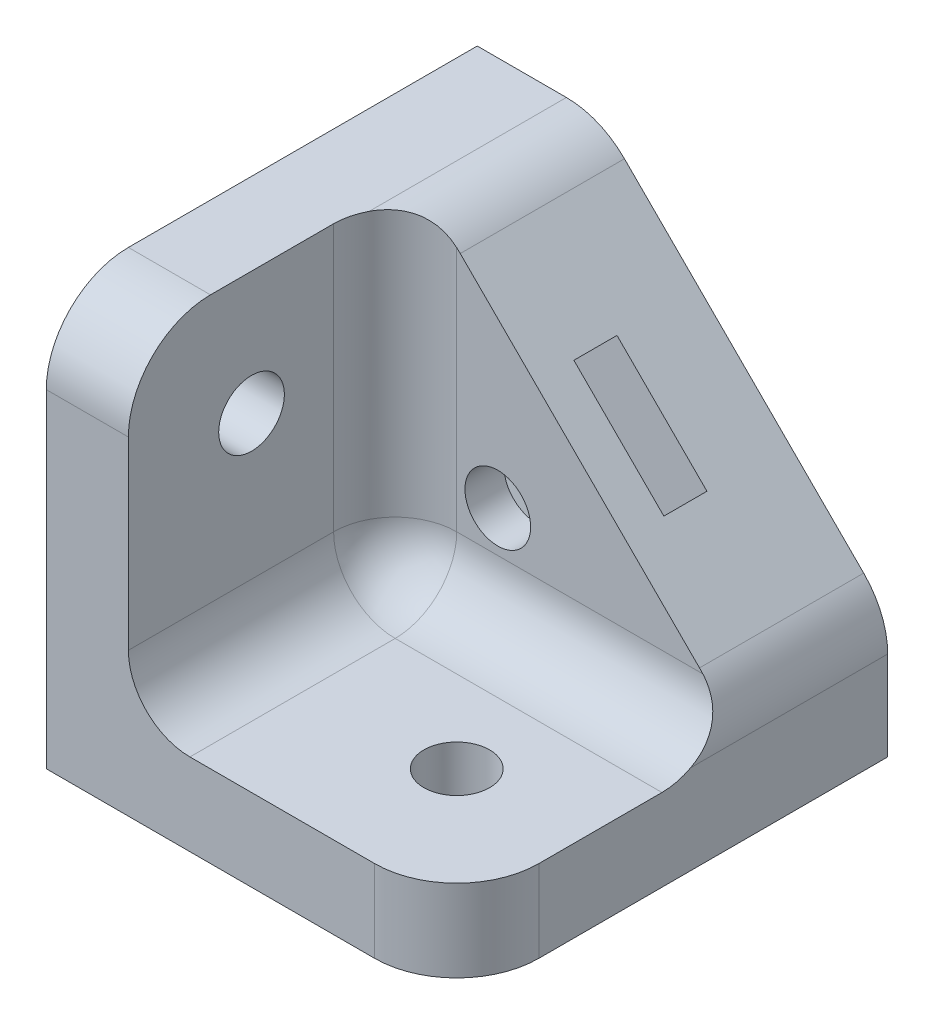
SolidWorks part; units mm, degrees
ref_plane "Front Plane" through (0, 0, 0) normal (0, 0, 1) x (1, 0, 0)
ref_plane "Top Plane" through (0, 0, 0) normal (0, 1, 0) x (1, 0, 0)
ref_plane "Right Plane" through (0, 0, 0) normal (1, 0, 0) x (0, 0, -1)
sketch "Sketch4" plane through (0, 0, 0) normal (0, 0, 1) x (1, 0, 0)
  line L2 (0, 0) -> (0, 20)
  line L3 (0, 20) -> (4, 20)
  line L4 (4, 4) -> (4, 20)
  line L5 (0, 0) -> (20, 0)
  line L7 (4, 4) -> (20, 4)
  line L8 (20, 0) -> (20, 4)
  line L9 (4, 20) -> (6, 20)
  line L10 (6, 20) -> (20, 6)
  line L11 (20, 6) -> (20, 4)
  dimension "D1" = 4
  dimension "D2" = 4
  dimension "D3" = 20
  dimension "D4" = 20
  dimension "D5" = 2
  dimension "D6" = 2
extrude "Boss-Extrude4" add sketch "Sketch4" along normal blind 8 separate body contours L5 L8 L7 L4 L3 L2 | L4 L7 region at (0.2828, 10, 0) region at (9.9325, 9.9325, 0)
extrude "Boss-Extrude5" add sketch "Sketch4<4>" along normal blind 21 contours L5 L8 L7 L4 L3 L2 region at (0.2828, 10, 0)
sketch "Sketch4<4>" plane through (0, 0, 0) normal (0, 0, 1) x (1, 0, 0) same geometry as "Sketch4"
sketch "Sketch5" plane through (13, 13, 0) normal (0.7071, 0.7071, 0) x (0, 0, -1)
  line L1 (-6.1, -3.1) -> (-4, -3.1)
  line L2 (-6.1, -3.1) -> (-6.1, 3.1)
  line L3 (-6.1, 3.1) -> (-4, 3.1)
  line L4 (-4, -3.1) -> (-4, 3.1)
  line L5 (-6.1, -3.1) -> (-4, 3.1) construction
  line L6 (-6.1, 3.1) -> (-4, -3.1) construction
  line L8 (0, 9.8995) -> (0, -9.8995) construction
  point P0 (-5.05, 0)
  dimension "D1" = 2.1
  dimension "D2" = 4
  dimension "D3" = 6.2
extrude "Cut-Extrude1" cut sketch "Sketch5" against normal blind 9
hole_wizard "Ø3.2 (3.2) Diameter Hole1" positions "3DSketch2" profile "Sketch6" hole size "Ø3.2" standard "ANSI Metric" end condition through all
sketch3d "3DSketch2"
  line L0 (0, 0, 21) -> (0, 0, 0) construction
  line L1 (0, 0, 0) -> (20, 0, 0) construction
  line L2 (0, 0, 0) -> (0, 20, 0) construction
  point P0 (14, 0, 15)
  point P2 (0, 14, 15)
  point P4 (9, 9, 0)
  dimension "D1" = 14
  dimension "D2" = 14
  dimension "D3" = 15
  dimension "D4" = 15
  dimension "D5" = 9
  dimension "D6" = 9
sketch "Sketch6" plane through (14, 0, 15) normal (1, 0, 0) x (0, 0, -1)
  line L0 (0, 0) -> (0, 20)
  line L1 (0, 20) -> (1.6, 20)
  line L2 (1.6, 20) -> (1.6, 0)
  line L5 (1.6, 0) -> (0, 0)
  line L11 (0, -6.35) -> (0, 107.95) construction
  dimension "Thru Hole Dia." = 3.2
  dimension "Thru Hole Depth" = 20
chamfer "Chamfer1" distance 1.5 angle 45 2 edges at (4.444, 8.8281, 5.05) (8.8281, 4.444, 5.05)
fillet "Fillet1" radius 3 3 edges at (12, 4, 8) (4, 4, 14.5) (4, 12, 8)
fillet "Fillet2" radius 4 4 edges at (6, 20, 4.0858) (20, 6, 4.0858) (20, 2, 21) (2, 20, 21)
equation "\"D2@Sketch4\"=\"D1@Sketch4\""
equation "\"D4@Sketch4\"=\"D3@Sketch4\""
equation "\"D6@Sketch4\"=\"D5@Sketch4\""
